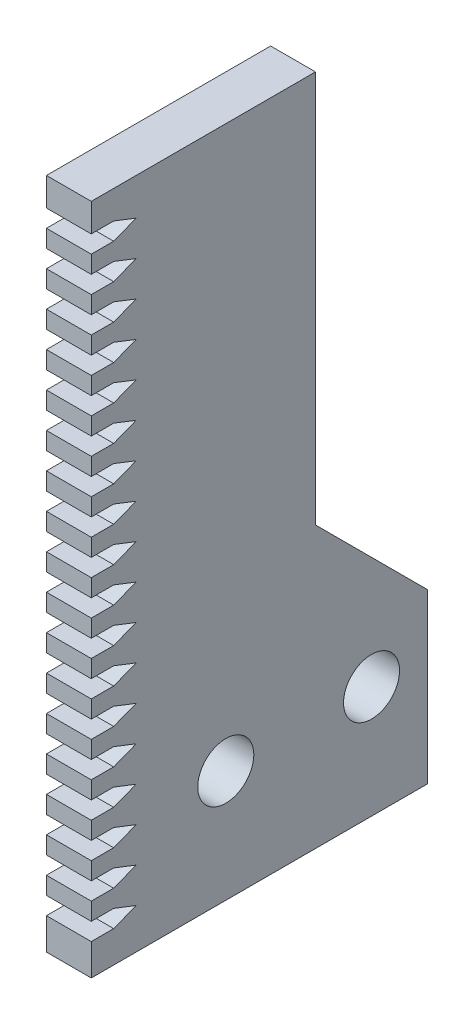
SolidWorks part; units mm, degrees
ref_plane "Спереди" through (0, 0, 0) normal (0, 0, 1) x (1, 0, 0)
ref_plane "Сверху" through (0, 0, 0) normal (0, 1, 0) x (1, 0, 0)
ref_plane "Справа" through (0, 0, 0) normal (1, 0, 0) x (0, 0, -1)
sketch "Эскиз1" plane through (0, 0, 0) normal (1, 0, 0) x (0, 0, -1)
  line L0 (30, 15) -> (20, 25)
  line L1 (0, 0) -> (30, 0)
  line L2 (0, 0) -> (0, 60)
  line L3 (0, 60) -> (20, 60)
  line L4 (30, 0) -> (30, 15)
  line L5 (20, 25) -> (20, 60)
  line L6 (0, 10) -> (30, 10) construction
  circle A0 centre (12, 10) radius 2.5
  circle A1 centre (25, 10) radius 2.5
  dimension "D7" = 5
  dimension "D1" = 30
  dimension "D2" = 60
  dimension "D3" = 20
  dimension "D4" = 15
  dimension "D5" = 10
  dimension "D6" = 10
  dimension "D8" = 12
  dimension "D9" = 5
  dimension "D10" = 13
extrude "Бобышка-Вытянуть1" add sketch "Эскиз1" along normal blind 4
sketch "Эскиз2" plane through (4, 0, 0) normal (1, 0, 0) x (0, 0, -1)
  line L0 (4, 60) -> (4, 0) construction
  line L1 (20, 60) -> (0, 60) construction
  line L2 (0, 0) -> (30, 0) construction
  line L3 (0, 60) -> (0, 0) construction
  line L4 (2, 60) -> (2, 4.3773) construction
  line L6 (4, 3.5963) -> (2, 4.3773)
  line L7 (4, 3.5963) -> (2, 2.8154)
  line L8 (0, 4.3773) -> (0, 2.8154)
  line L9 (0, 2.8154) -> (2, 2.8154)
  line L11 (0, 4.3773) -> (2, 4.3773)
  line L12 (2, 2.8154) -> (2, 0) construction
  dimension "D1" = 4
  dimension "D2" = 2
  dimension "D3" = 1.5619
extrude "Вырез-Вытянуть1" cut sketch "Эскиз2" against normal blind 4
pattern_linear "Линейный массив1" count 18 spacing 3.1237 along (0, 1, 0) of "Вырез-Вытянуть1"
